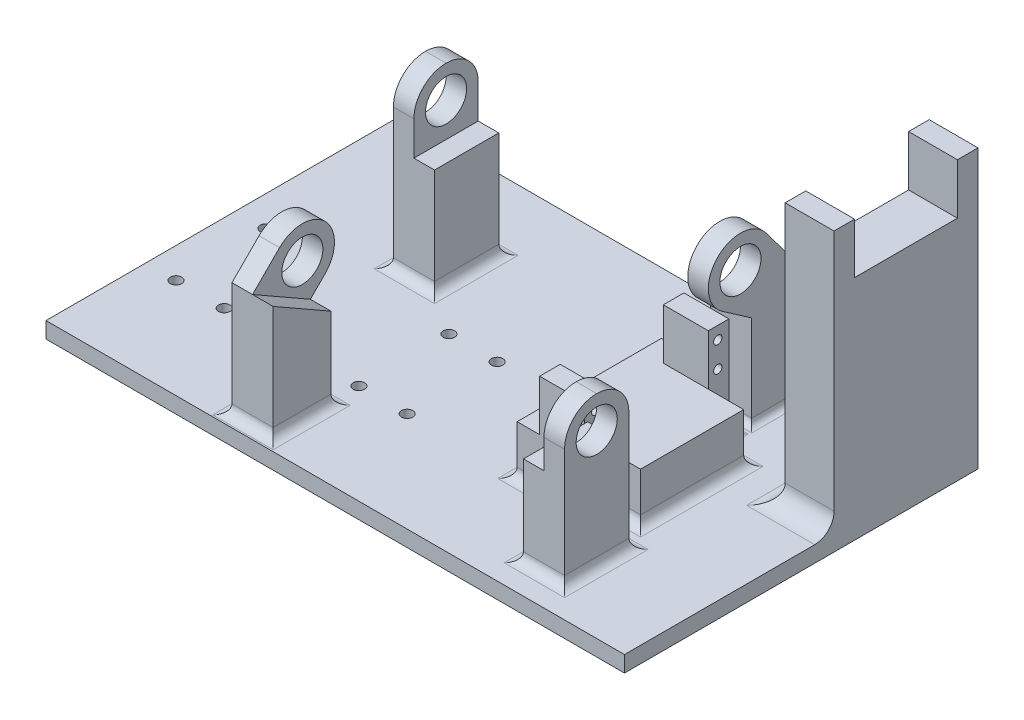
SolidWorks part; units mm, degrees
ref_plane "Front Plane" through (0, 0, 0) normal (0, 0, 1) x (1, 0, 0)
ref_plane "Top Plane" through (0, 0, 0) normal (0, 1, 0) x (1, 0, 0)
ref_plane "Right Plane" through (0, 0, 0) normal (1, 0, 0) x (0, 0, -1)
sketch "Sketch2" plane through (0, 0, 0) normal (0, 1, 0) x (1, 0, 0)
  line L1 (-147.9924, 43.5815) -> (80.6076, 43.5815)
  line L2 (-147.9924, 43.5815) -> (-147.9924, -96.1185)
  line L3 (-147.9924, -96.1185) -> (80.6076, -96.1185)
  line L4 (80.6076, 43.5815) -> (80.6076, -96.1185)
  dimension "D1" = 228.6
  dimension "D2" = 139.7
extrude "Boss-Extrude1" add sketch "Sketch2" along normal blind 6.35
sketch "Sketch3" plane through (0, 6.35, 0) normal (0, 1, 0) x (1, 0, 0)
  line L0 (-147.9924, -96.1185) -> (80.6076, -96.1185) construction
  line L1 (37.3769, -59.2885) -> (45.5049, -59.2885)
  line L2 (37.3769, -59.2885) -> (37.3769, -84.6885)
  line L3 (37.3769, -84.6885) -> (45.5049, -84.6885)
  line L4 (45.5049, -59.2885) -> (45.5049, -84.6885)
  dimension "D1" = 8.128
  dimension "D2" = 11.43
  dimension "D3" = 25.4
extrude "Boss-Extrude2" add sketch "Sketch3" along normal blind 59.69
fillet "Fillet3" radius 12.7 2 edges at (41.4409, 66.04, 84.6885) (41.4409, 66.04, 59.2885)
sketch "Sketch5" plane through (45.5049, 0, 0) normal (1, 0, 0) x (0, 0, -1)
  line L1 (-84.6885, 6.35) -> (-59.2885, 6.35) construction
  circle A0 centre (-71.9885, 53.34) radius 8.128
  arc A1 (-59.2885, 53.34) -> (-71.9885, 66.04) centre (-71.9885, 53.34) ccw construction
  dimension "D1" = 46.99
  dimension "D2" = 16.256
extrude "Cut-Extrude1" cut sketch "Sketch5" against normal blind 53.34
sketch "Sketch7" plane through (0, 6.35, 0) normal (0, 1, 0) x (1, 0, 0)
  line L0 (37.3769, -59.2885) -> (37.3769, -71.9885) construction
  line L1 (37.3769, -59.2885) -> (29.2489, -59.2885)
  line L2 (37.3769, -59.2885) -> (37.3769, -84.6885)
  line L3 (37.3769, -84.6885) -> (29.2489, -84.6885)
  line L4 (29.2489, -59.2885) -> (29.2489, -84.6885)
  dimension "D1" = 8.128
extrude "Boss-Extrude3" add sketch "Sketch7" along normal blind 35.56
sketch "Sketch8" plane through (0, 6.35, 0) normal (0, 1, 0) x (1, 0, 0)
  line L1 (-70.8271, -68.8135) -> (-78.9551, -68.8135)
  line L2 (-70.8271, -68.8135) -> (-70.8271, -91.6735)
  line L3 (-70.8271, -91.6735) -> (-78.9551, -91.6735)
  line L4 (-78.9551, -68.8135) -> (-78.9551, -91.6735)
  line L5 (45.5049, -59.2885) -> (29.2489, -59.2885) construction
  line L7 (45.5049, -84.6885) -> (45.5049, -59.2885) construction
  dimension "D1" = 8.128
  dimension "D2" = 22.86
  dimension "D3" = 9.525
  dimension "D4" = 124.46
extrude "Boss-Extrude4" add sketch "Sketch8" along normal blind 25.4
sketch "Sketch9" plane through (-78.9551, 0, 0) normal (-1, 0, 0) x (0, 0, 1)
  line L0 (91.6735, 31.75) -> (91.6735, 51.6155)
  line L1 (91.6735, 51.6155) -> (71.9885, 71.3005)
  line L2 (71.9885, 71.3005) -> (54.0279, 53.34)
  line L3 (54.0279, 53.34) -> (68.8135, 38.5545)
  line L4 (68.8135, 38.5545) -> (68.8135, 31.75)
  line L5 (68.8135, 31.75) -> (91.6735, 31.75) construction
  line L6 (68.8135, 31.75) -> (68.8135, 6.35) construction
  line L11 (68.8135, 6.35) -> (91.6735, 6.35)
  line L12 (91.6735, 6.35) -> (91.6735, 31.75)
  line L13 (91.6735, 31.75) -> (68.8135, 31.75)
  line L14 (68.8135, 31.75) -> (68.8135, 6.35)
  line L17 (91.6735, 31.75) -> (68.8135, 31.75)
  circle A0 centre (71.9885, 53.34) radius 8.128 construction
  arc A1 (84.6885, 53.34) -> (71.9885, 66.04) centre (71.9885, 53.34) ccw construction
  dimension "D1" = 25.4
  dimension "D2" = 12.7
  dimension "D3" = 135
  dimension "D4" = 0
extrude "Boss-Extrude5" add sketch "Sketch9" against normal blind 8.128
fillet "Fillet4" radius 12.7 2 edges at (-74.8911, 53.34, 54.0279) (-74.8911, 71.3005, 71.9885)
sketch "Sketch10" plane through (-78.9551, 0, 0) normal (-1, 0, 0) x (0, 0, 1)
  circle A0 centre (71.9885, 53.34) radius 8.128
  arc A1 (80.9687, 62.3203) -> (63.0082, 62.3203) centre (71.9885, 53.34) ccw construction
  dimension "D1" = 16.256
extrude "Cut-Extrude2" cut sketch "Sketch10" against normal blind 8.128
sketch "Sketch11" plane through (0, 6.35, 0) normal (0, 1, 0) x (1, 0, 0)
  line L1 (-70.8271, -91.6735) -> (-62.6991, -91.6735)
  line L2 (-70.8271, -91.6735) -> (-70.8271, -68.8135)
  line L3 (-70.8271, -68.8135) -> (-62.6991, -68.8135)
  line L4 (-62.6991, -91.6735) -> (-62.6991, -68.8135)
  dimension "D1" = 8.128
  dimension "D2" = 22.86
extrude "Boss-Extrude6" add sketch "Sketch11" along normal up to vertex (32.2045 mm away)
sketch "Sketch12" plane through (-70.8271, 0, 0) normal (1, 0, 0) x (0, 0, -1)
  line L0 (-91.6735, 51.6155) -> (-68.8135, 38.5545)
  line L1 (-68.8135, 38.5545) -> (-91.6735, 38.5545)
  line L2 (-91.6735, 38.5545) -> (-91.6735, 51.6155)
extrude "Boss-Extrude7" add sketch "Sketch12" along normal up to vertex
sketch "Sketch13" plane through (0, 6.35, 0) normal (0, 1, 0) x (1, 0, 0)
  line L0 (80.6076, 43.5815) -> (-147.9924, 43.5815) construction
  line L1 (-0.8696, -48.938) -> (39.7704, -48.938)
  line L2 (-0.8696, -48.938) -> (-0.8696, -8.171)
  line L3 (-0.8696, -8.171) -> (39.7704, -8.171)
  line L4 (39.7704, -48.938) -> (39.7704, -8.171)
  dimension "D1" = 40.64
  dimension "D2" = 40.767
  dimension "D3" = 51.7525
extrude "Boss-Extrude8" add sketch "Sketch13" along normal up to vertex (19.4334 mm away)
sketch "Sketch14" plane through (0, 6.35, 0) normal (0, 1, 0) x (1, 0, 0)
  line L1 (-0.8696, -48.938) -> (25.8004, -48.938)
  line L2 (-0.8696, -48.938) -> (-0.8696, -57.066)
  line L3 (-0.8696, -57.066) -> (25.8004, -57.066)
  line L4 (25.8004, -48.938) -> (25.8004, -57.066)
  line L5 (-0.8696, -8.171) -> (25.8004, -8.171)
  line L6 (-0.8696, -8.171) -> (-0.8696, -0.043)
  line L7 (-0.8696, -0.043) -> (25.8004, -0.043)
  line L8 (25.8004, -8.171) -> (25.8004, -0.043)
  dimension "D1" = 26.67
  dimension "D2" = 26.67
  dimension "D3" = 8.128
extrude "Boss-Extrude9" add sketch "Sketch14" along normal up to vertex (39.4334 mm away)
fillet "Fillet6" radius 3.81 16 edges at (25.8004, 6.35, 4.107) (32.7854, 6.35, 8.171) (12.4654, 6.35, 0.043) (39.7704, 6.35, 28.5545) (25.8004, 6.35, 53.002) (32.7854, 6.35, 48.938) (-0.8696, 6.35, 28.5545) (12.4654, 6.35, 57.066) (37.3769, 6.35, 59.2885) (45.5049, 6.35, 71.9885) (37.3769, 6.35, 84.6885) (29.2489, 6.35, 71.9885) (-70.8271, 6.35, 68.8135) (-78.9551, 6.35, 80.2435) (-70.8271, 6.35, 91.6735) (-62.6991, 6.35, 80.2435)
sketch "Sketch15" plane through (25.8004, 0, 0) normal (1, 0, 0) x (0, 0, -1)
  circle A0 centre (-4.4323, 40.7834) radius 1.651
  circle A1 centre (-4.4323, 30.7834) radius 1.651
  circle A2 centre (-52.6323, 40.7834) radius 1.651
  circle A3 centre (-52.6323, 30.7834) radius 1.651
  dimension "D1" = 3.302
extrude "Cut-Extrude3" cut sketch "Sketch15" against normal blind 12.7
sketch "Sketch16" plane through (0, 45.7834, 0) normal (0, 1, 0) x (1, 0, 0)
  line L0 (25.8004, -0.043) -> (-0.8696, -0.043) construction
  line L1 (-0.8696, -8.171) -> (8.0204, -8.171)
  line L2 (-0.8696, -8.171) -> (-0.8696, -0.043)
  line L3 (-0.8696, -0.043) -> (8.0204, -0.043)
  line L4 (8.0204, -8.171) -> (8.0204, -0.043)
  line L5 (25.8004, -48.938) -> (-0.8696, -48.938) construction
  line L6 (-0.8696, -57.066) -> (8.0204, -57.066)
  line L7 (-0.8696, -57.066) -> (-0.8696, -48.938)
  line L8 (-0.8696, -48.938) -> (8.0204, -48.938)
  line L9 (8.0204, -57.066) -> (8.0204, -48.938)
  dimension "D1" = 8.89
extrude "Cut-Extrude4" cut sketch "Sketch16" against normal up to vertex
sketch "Sketch17" plane through (0, 6.35, 0) normal (0, 1, 0) x (1, 0, 0)
  line L0 (-98.3561, -3.5355) -> (-98.3561, 9.4185) construction
  line L1 (-97.0861, -9.7585) -> (-88.9581, -9.7585)
  line L2 (-97.0861, -9.7585) -> (-97.0861, 15.6415)
  line L3 (-97.0861, 15.6415) -> (-88.9581, 15.6415)
  line L4 (-88.9581, -9.7585) -> (-88.9581, 15.6415)
  line L5 (80.6076, 43.5815) -> (-147.9924, 43.5815) construction
  dimension "D1" = 25.4
  dimension "D2" = 8.128
  dimension "D3" = 1.27
  dimension "D4" = 27.94
extrude "Boss-Extrude10" add sketch "Sketch17" along normal blind 68.072
fillet "Fillet7" radius 12.7 2 edges at (-93.0221, 74.422, 9.7585) (-93.0221, 74.422, -15.6415)
sketch "Sketch20" plane through (-88.9581, 0, 0) normal (1, 0, 0) x (0, 0, -1)
  circle A0 centre (2.9415, 61.722) radius 8.128
  arc A1 (2.9415, 74.422) -> (-9.7585, 61.722) centre (2.9415, 61.722) ccw construction
  dimension "D1" = 16.256
extrude "Cut-Extrude5" cut sketch "Sketch20" against normal blind 17.78
sketch "Sketch21" plane through (0, 6.35, 0) normal (0, 1, 0) x (1, 0, 0)
  line L1 (-88.9581, 15.6415) -> (-80.8301, 15.6415)
  line L2 (-88.9581, 15.6415) -> (-88.9581, -9.7585)
  line L3 (-88.9581, -9.7585) -> (-80.8301, -9.7585)
  line L4 (-80.8301, 15.6415) -> (-80.8301, -9.7585)
  dimension "D1" = 25.4
  dimension "D2" = 8.128
extrude "Boss-Extrude11" add sketch "Sketch21" along normal blind 41.91
fillet "Fillet8" radius 3.81 4 edges at (-88.9581, 6.35, 9.7585) (-97.0861, 6.35, -2.9415) (-80.8301, 6.35, -2.9415) (-88.9581, 6.35, -15.6415)
sketch "Sketch22" plane through (0, 6.35, 0) normal (0, 1, 0) x (1, 0, 0)
  line L0 (80.6076, 43.5815) -> (-147.9924, 43.5815) construction
  line L1 (27.3739, 7.3865) -> (19.2459, 7.3865)
  line L2 (27.3739, 7.3865) -> (27.3739, 32.7865)
  line L3 (27.3739, 32.7865) -> (19.2459, 32.7865)
  line L4 (19.2459, 7.3865) -> (19.2459, 32.7865)
  dimension "D1" = 25.4
  dimension "D2" = 8.128
  dimension "D3" = 10.795
  dimension "D4" = 1.27
extrude "Boss-Extrude12" add sketch "Sketch22" along normal blind 36.83
sketch "Sketch23" plane through (19.2459, 0, 0) normal (-1, 0, 0) x (0, 0, 1)
  line L0 (-32.7865, 43.18) -> (-13.0897, 69.3578)
  line L1 (4.2984, 51.2878) -> (-7.3865, 43.18)
  arc A0 (-13.0897, 69.3578) -> (4.2984, 51.2878) centre (-2.9415, 61.722) cw
  arc A1 (9.7585, 61.722) -> (-2.9415, 74.422) centre (-2.9415, 61.722) ccw construction
  circle A2 centre (-2.9415, 61.722) radius 8.128
  line M5 (-7.3865, 43.18) -> (-32.7865, 43.18)
extrude "Boss-Extrude13" add sketch "Sketch23" against normal up to surface (8.128 mm away) contours A0 L0 L1 A2 M5 up to face at (27.3739, 24.765, -20.0865)
sketch "Sketch24" plane through (0, 6.35, 0) normal (0, 1, 0) x (1, 0, 0)
  line L1 (19.2459, 7.3865) -> (11.1179, 7.3865)
  line L2 (19.2459, 7.3865) -> (19.2459, 32.7865)
  line L3 (19.2459, 32.7865) -> (11.1179, 32.7865)
  line L4 (11.1179, 7.3865) -> (11.1179, 32.7865)
  dimension "D1" = 8.128
extrude "Boss-Extrude14" add sketch "Sketch24" along normal blind 36.83
fillet "Fillet10" radius 2.54 4 edges at (27.3739, 6.35, -20.0865) (19.2459, 6.35, -7.3865) (19.2459, 6.35, -32.7865) (11.1179, 6.35, -20.0865)
sketch "Sketch26" plane through (0, 6.35, 0) normal (0, 1, 0) x (1, 0, 0)
  line L1 (80.6076, 43.5815) -> (61.3036, 43.5815)
  line L2 (80.6076, 43.5815) -> (80.6076, -13.3145)
  line L3 (80.6076, -13.3145) -> (61.3036, -13.3145)
  line L4 (61.3036, 43.5815) -> (61.3036, -13.3145)
  dimension "D1" = 56.896
  dimension "D2" = 19.304
extrude "Boss-Extrude15" add sketch "Sketch26" along normal up to surface (83.5464 mm away)
sketch "Sketch27" plane through (0, 89.8964, 0) normal (0, 1, 0) x (1, 0, 0)
  line L0 (61.3036, -13.3145) -> (61.3036, 43.5815) construction
  line L1 (80.6076, -13.3145) -> (61.3036, -13.3145)
  line L2 (80.6076, -13.3145) -> (80.6076, -5.1865)
  line L3 (80.6076, -5.1865) -> (61.3036, -5.1865)
  line L4 (61.3036, -13.3145) -> (61.3036, -5.1865)
  line L6 (80.6076, 43.5815) -> (61.3036, 43.5815)
  line L7 (80.6076, 43.5815) -> (80.6076, 35.4535)
  line L8 (80.6076, 35.4535) -> (61.3036, 35.4535)
  line L9 (61.3036, 43.5815) -> (61.3036, 35.4535)
  dimension "D1" = 8.128
  dimension "D2" = 8.128
extrude "Boss-Extrude16" add sketch "Sketch27" along normal up to surface (20 mm away)
sketch "Sketch28" plane through (61.3036, 0, 0) normal (-1, 0, 0) x (0, 0, 1)
  circle A0 centre (8.9005, 104.8964) radius 1.625
  circle A1 centre (8.9005, 94.8964) radius 1.625
  circle A2 centre (-39.2995, 104.8964) radius 1.625
  circle A3 centre (-39.2995, 94.8964) radius 1.625
extrude "Cut-Extrude6" cut sketch "Sketch28" against normal blind 8.89
fillet "Fillet11" radius 7.62 2 edges at (70.9556, 6.35, 13.3145) (61.3036, 6.35, -15.1335)
sketch "Sketch29" plane through (0, 6.35, 0) normal (0, 1, 0) x (1, 0, 0)
  circle A0 centre (-136.0564, -56.6831) radius 2.25
  circle A1 centre (-117.0064, -56.6831) radius 2.25
  circle A2 centre (-136.0564, -21.1231) radius 2.25
  circle A3 centre (-117.0064, -21.1231) radius 2.25
  circle A4 centre (-44.7124, -56.6831) radius 2.25
  circle A5 centre (-63.7624, -56.6831) radius 2.25
  circle A6 centre (-44.7124, -21.1231) radius 2.25
  circle A7 centre (-63.7624, -21.1231) radius 2.25
extrude "Cut-Extrude7" cut sketch "Sketch29" against normal blind 11.43
